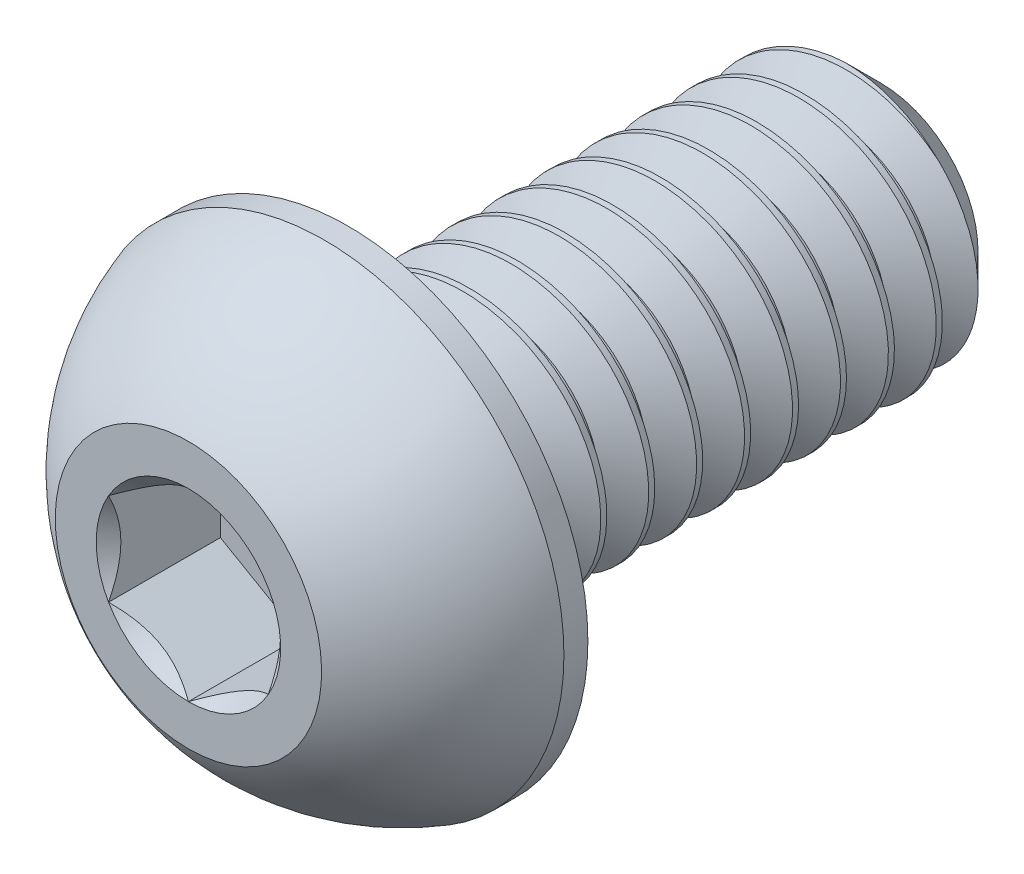
SolidWorks part; units mm, degrees
note: '?' marks a value the reader was unsure of.
ref_plane "Front" through (0, 0, 0) normal (0, 0, 1) x (1, 0, 0)
ref_plane "Top" through (0, 0, 0) normal (0, 1, 0) x (1, 0, 0)
ref_plane "Right" through (0, 0, 0) normal (1, 0, 0) x (0, 0, -1)
sketch "Sketch1" plane through (0, 0, 0) normal (1, 0, 0) x (0, 0, -1)
  line L2 (1.5, 1.25) -> (6.5, 1.25)
  line L3 (6.5, 1.25) -> (6.5, 0)
  line L4 (6.5, 0) -> (1.5, 0)
  line L6 (1.275, 2.25) -> (1.5, 2.25) construction
  line L7 (6.5, 1.25) -> (6.5, -1.25) construction
  line L8 (0, 0) -> (1.5, 0) construction
  line L9 (1.5, 2.25) -> (1.5, -2.25) construction
  line L11 (1.5, 1.25) -> (1.5, 0)
  line L13 (0, 0.75) -> (0, -0.75) construction
  line L14 (0, 0.75) -> (0, 1.25) construction
  arc A3 (0, 1.25) -> (1.275, 2.25) centre (2.01, 0) cw construction
  dimension "D1" = 0.225
revolve "Revolve1" add sketch "Sketch1" angle 360 mid plane about L4
sketch "Sketch3" plane through (0, 0, -6.5) normal (0, 0, -1) x (-1, 0, 0)
  circle A0 centre (0, 0) radius 1.25
curve "Helix/Spiral1" pitch 0.45 height 5.45 turns 12.1111
chamfer "Chamfer1" distance 0.3375 angle 45 1 edges at (0, 1.25, -6.5)
sketch "Sketch7" plane through (0, 0, 0) normal (1, 0, 0) x (0, 0, -1)
  line L6 (1.275, 2.25) -> (1.5, 2.25) construction
  line L8 (0, 0) -> (1.5, 0) construction
  line L11 (1.5, 2.25) -> (1.5, -2.25) construction
  line L12 (1.275, 2.25) -> (1.5, 2.25)
  line L13 (0, 0) -> (1.5, 0)
  line L14 (0, 0.75) -> (0, -0.75) construction
  line L15 (1.5, 2.25) -> (1.5, 0)
  line L16 (0, 1.25) -> (0, 0)
  arc A2 (1.275, 2.25) -> (0, 1.25) centre (2.01, 0) ccw construction
  arc A3 (1.275, 2.25) -> (0, 1.25) centre (2.01, 0) ccw
revolve "Revolve2" add sketch "Sketch7" angle 360 mid plane about L13
sketch "Sketch5" plane through (0, 0, 0) normal (0, 0, 1) x (1, 0, 0)
  line L1 (0.75, -0.433) -> (0.75, 0.433)
  line L2 (0.75, 0.433) -> (0, 0.866)
  line L3 (0, 0.866) -> (-0.75, 0.433)
  line L4 (-0.75, 0.433) -> (-0.75, -0.433)
  line L5 (-0.75, -0.433) -> (0, -0.866)
  line L6 (0, -0.866) -> (0.75, -0.433)
  circle A0 centre (0, 0) radius 0.75 construction
extrude "Cut-Extrude2" cut sketch "Sketch5" against normal blind 1.05
sketch "Sketch6" plane through (0, 0, 0) normal (0, 0, 1) x (1, 0, 0)
  circle A0 centre (0, 0) radius 0.866
extrude "Cut-Extrude3" cut sketch "Sketch6" against normal blind 1.05 draft 45
sketch "Sketch2" plane through (0, 0, 0) normal (1, 0, 0) x (0, 0, -1)
  line L0 (6.1625, 1.25) -> (6.5562, 1.25)
  line L1 (6.5562, 1.25) -> (6.3875, 0.9577)
  line L2 (6.3875, 0.9577) -> (6.3312, 0.9577)
  line L3 (6.3312, 0.9577) -> (6.1625, 1.25)
  line L4 (6.2469, 1.1039) -> (6.4719, 1.1039) construction
  dimension "D1" = 60
  dimension "D2" = 0.0563
  dimension "D3" = 0.225
sweep "Cut-Sweep1" cut profiles "Sketch2" path "Helix/Spiral1"
sketch "Sketch10" plane through (0, 0, 0) normal (1, 0, 0) x (0, 0, -1)
  line L0 (6.5, 1.25) -> (6.5, -1.25) construction
  point P0 (5.825, -1.25)
  dimension "D1" = 0.675
ref_axis "Center Axis 1" through (0, 0, -8.1113) along (0, 0, 1)?
ref_plane "Contact Plane 1" through (0, 0, -1.5) normal (0, 0, -1) x (-1, 0, 0)
ref_plane "Contact Plane 2" through (0, 0, 0) normal (0, 0, 1) x (1, 0, 0)
equation "\"D3@Helix/Spiral1\" = \"Lg@Sketch1\" + \"D4@Helix/Spiral1\""
equation "\"D2@Sketch2\" = \"D4@Helix/Spiral1\" * .125"
equation "\"D3@Sketch2\" = \"D4@Helix/Spiral1\" * .5"
equation "\"D1@Chamfer1\" = \"D4@Helix/Spiral1\" * .75"
equation "\"D1@Cut-Extrude2\" = \"Head Ht@Sketch1\" * .7"
equation "\"D1@Sketch1\" = \"Head Ht@Sketch1\" * .15"
equation "\"D1@Sketch10\" = \"D4@Helix/Spiral1\" * 1.5"
equation "\"D1@Cut-Extrude3\" = \"D1@Cut-Extrude2\""
